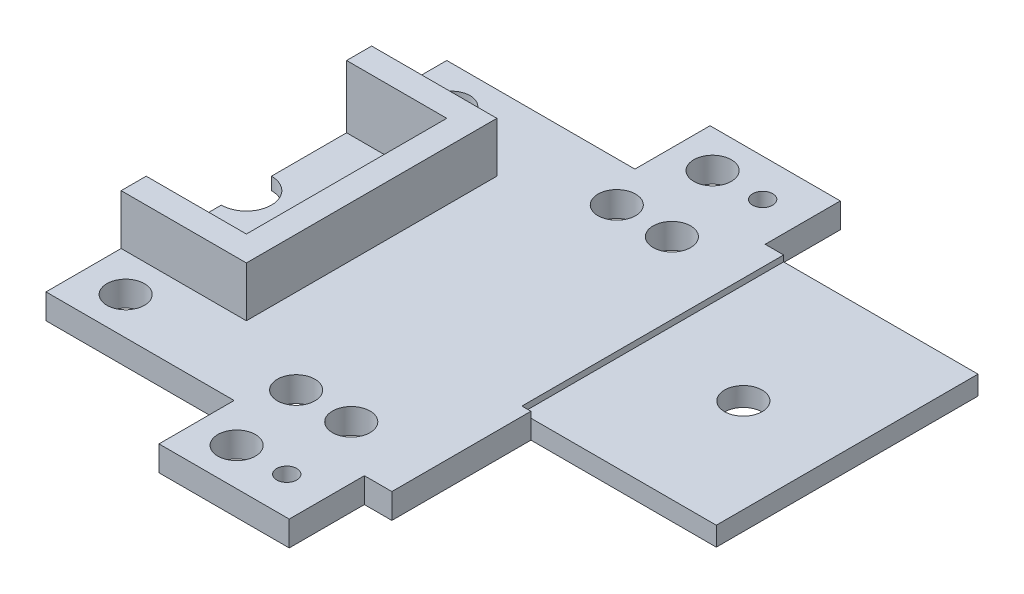
SolidWorks part; units mm, degrees
ref_plane "Front Plane" through (0, 0, 0) normal (0, 0, 1) x (1, 0, 0)
ref_plane "Top Plane" through (0, 0, 0) normal (0, 1, 0) x (1, 0, 0)
ref_plane "Right Plane" through (0, 0, 0) normal (1, 0, 0) x (0, 0, -1)
sketch "Sketch1" plane through (0, 0, 0) normal (0, 1, 0) x (1, 0, 0)
  line L1 (-279.4, -50.8) -> (0, -50.8)
  line L2 (-279.4, -50.8) -> (-279.4, 50.8)
  line L3 (-279.4, 50.8) -> (0, 50.8)
  line L4 (0, -50.8) -> (0, 50.8)
  point P0 (0, 0)
  dimension "D1" = 279.4
  dimension "D2" = 101.6
  dimension "D3" = 50.8
extrude "Boss-Extrude1" add sketch "Sketch1" along normal blind 6.35
sketch "Sketch2" plane through (0, 6.35, 0) normal (0, 1, 0) x (1, 0, 0)
  line L0 (-279.4, 50.8) -> (-279.4, -50.8) construction
  line L2 (0, 50.8) -> (-279.4, 50.8) construction
  circle A0 centre (-258.5106, 0) radius 13.97
  dimension "D1" = 50.8
  dimension "D2" = 27.94
  dimension "D3" = 20.8894
extrude "Boss-Extrude3" add sketch "Sketch2" along normal blind 5.5562
sketch "Sketch9" plane through (0, 11.9062, 0) normal (0, 1, 0) x (1, 0, 0)
  circle A0 centre (-258.5106, 0) radius 11.1125
  dimension "D1" = 22.225
extrude "Cut-Extrude4" cut sketch "Sketch9" against normal blind 4.445
sketch "Sketch10" plane through (0, 0, 0) normal (0, -1, 0) x (-1, 0, 0)
  circle A0 centre (258.5106, 0) radius 11.1125
  dimension "D1" = 22.225
extrude "Cut-Extrude5" cut sketch "Sketch10" against normal blind 5.5562
sketch "Sketch11" plane through (0, 7.4613, 0) normal (0, 1, 0) x (1, 0, 0)
  circle A0 centre (-258.5106, 0) radius 7.9375
  dimension "D1" = 15.875
extrude "Cut-Extrude6" cut sketch "Sketch11" against normal through all
sketch "Sketch12" plane through (0, 6.35, 0) normal (0, 1, 0) x (1, 0, 0)
  line L0 (0, 50.8) -> (-279.4, 50.8) construction
  line L1 (-279.4, 50.8) -> (-279.4, -50.8) construction
  circle A0 centre (-134.6662, 0) radius 6.35
  dimension "D1" = 12.7
  dimension "D2" = 50.8
  dimension "D3" = 144.7338
extrude "Cut-Extrude7" cut sketch "Sketch12" against normal through all
sketch "Sketch22" plane through (0, 6.35, 0) normal (0, 1, 0) x (1, 0, 0)
  line L1 (-102.9162, -31.75) -> (-166.4162, -31.75)
  line L2 (-102.9162, -31.75) -> (-102.9162, 31.75)
  line L3 (-102.9162, 31.75) -> (-166.4162, 31.75)
  line L4 (-166.4162, -31.75) -> (-166.4162, 31.75)
  line L5 (-102.9162, -31.75) -> (-166.4162, 31.75) construction
  line L6 (-102.9162, 31.75) -> (-166.4162, -31.75) construction
  circle A0 centre (-134.6662, 0) radius 6.35 construction
  point P0 (-134.6662, 0)
  dimension "D1" = 63.5
  dimension "D2" = 63.5
extrude "Boss-Extrude7" add sketch "Sketch22" along normal blind 12.7
sketch "Sketch25" plane through (0, 19.05, 0) normal (0, 1, 0) x (1, 0, 0)
  line L1 (-109.2662, -25.4) -> (-160.0662, -25.4)
  line L2 (-109.2662, -25.4) -> (-109.2662, 25.4)
  line L3 (-109.2662, 25.4) -> (-160.0662, 25.4)
  line L4 (-160.0662, -25.4) -> (-160.0662, 25.4)
  line L5 (-109.2662, -25.4) -> (-160.0662, 25.4) construction
  line L6 (-109.2662, 25.4) -> (-160.0662, -25.4) construction
  circle A0 centre (-134.6662, 0) radius 6.35 construction
  point P0 (-134.6662, 0)
  dimension "D1" = 50.8
  dimension "D2" = 50.8
extrude "Cut-Extrude11" cut sketch "Sketch25" against normal blind 15.875
sketch "Sketch32" plane through (0, 6.35, 0) normal (0, 1, 0) x (1, 0, 0)
  line L0 (0, -50.8) -> (0, 50.8) construction
  line L3 (-279.4, -50.8) -> (0, -50.8) construction
  line L5 (0, 50.8) -> (-279.4, 50.8) construction
  circle A0 centre (-67.442, -40.64) radius 4.7625
  circle A1 centre (-81.412, -40.64) radius 4.7625
  circle A2 centre (-67.442, 40.64) radius 4.7625
  circle A3 centre (-81.412, 40.64) radius 4.7625
  dimension "D1" = 10.16
  dimension "D2" = 10.16
  dimension "D3" = 10.16
  dimension "D4" = 10.16
  dimension "D9" = 9.525
  dimension "D10" = 9.525
  dimension "D11" = 9.525
  dimension "D12" = 9.525
  dimension "D5" = 13.97
  dimension "D6" = 13.97
  dimension "D7" = 81.28
  dimension "D8" = 81.412
extrude "Cut-Extrude12" cut sketch "Sketch32" against normal blind 6.35
sketch "Sketch38" plane through (0, 6.35, 0) normal (0, 1, 0) x (1, 0, 0)
  line L0 (0, -50.8) -> (0, 50.8) construction
  line L1 (0, -34.0128) -> (-46.99, -34.0128)
  line L2 (0, -34.0128) -> (0, -15.5426)
  line L3 (0, -15.5426) -> (-46.99, -15.5426)
  line L4 (-46.99, -34.0128) -> (-46.99, -15.5426)
  line L6 (-279.4, -50.8) -> (0, -50.8) construction
  dimension "D1" = 35.2574
  dimension "D2" = 18.4703
  dimension "D3" = 46.99
extrude "Cut-Extrude13" cut sketch "Sketch38" against normal blind 6.35
sketch "Sketch60" plane through (0, 6.35, 0) normal (0, 1, 0) x (1, 0, 0)
  line L1 (-279.4, 50.8) -> (-279.4, -50.8) construction
  line L2 (0, 50.8) -> (-279.4, 50.8) construction
  circle A0 centre (-231.7492, 41.3241) radius 4.7625
  circle A1 centre (-231.7492, -39.3693) radius 4.7625
  circle A2 centre (-173.5092, -39.3693) radius 4.7625
  circle A3 centre (-173.5092, 41.3241) radius 4.7625
  dimension "D1" = 47.6508
  dimension "D5" = 9.525
  dimension "D6" = 9.525
  dimension "D7" = 9.525
  dimension "D8" = 9.525
  dimension "D2" = 58.24
  dimension "D3" = 80.6935
  dimension "D4" = 9.4759
  dimension "D9" = 105.8908
extrude "Cut-Extrude23" cut sketch "Sketch60" against normal up to surface (6.35 mm away) up to face at (-81.5975, 0, 12.3889)
sketch "Sketch64" plane through (0, 6.35, 0) normal (0, 1, 0) x (1, 0, 0)
  line L0 (-279.4, -50.8) -> (0, -50.8) construction
  circle A0 centre (-145.3342, -41.275) radius 4.7625
  circle A1 centre (-123.9982, -41.275) radius 4.7625
  circle A3 centre (-134.6662, 0) radius 6.35 construction
  dimension "D1" = 21.336
  dimension "D3" = 9.525
  dimension "D4" = 9.525
  dimension "D2" = 10.668
  dimension "D5" = 9.525
  dimension "D6" = 9.525
extrude "Cut-Extrude24" cut sketch "Sketch64" against normal through all
mirror "Mirror1" about plane through (0, 0, 0) normal (0, 0, 1) of "Cut-Extrude24"
sketch "Sketch69" plane through (0, 0, 50.8) normal (0, 0, 1) x (1, 0, 0)
  line L0 (-279.4, 6.35) -> (0, 6.35) construction
  line L1 (-86.9754, 6.35) -> (-53.9554, 6.35)
  line L2 (-86.9754, 6.35) -> (-86.9754, 0)
  line L3 (-86.9754, 0) -> (-53.9554, 0)
  line L4 (-53.9554, 6.35) -> (-53.9554, 0)
  line L5 (-279.4, 0) -> (0, 0) construction
  line L7 (0, 6.35) -> (0, 0) construction
  dimension "D1" = 33.02
  dimension "D2" = 53.9554
extrude "Boss-Extrude10" add sketch "Sketch69" along normal blind 19.05
sketch "Sketch70" plane through (0, 6.35, 0) normal (0, 1, 0) x (1, 0, 0)
  line L1 (-86.9754, -69.85) -> (-86.9754, -50.8) construction
  circle A0 centre (-76.8154, -60.325) radius 4.7625
  circle A1 centre (-64.1154, -60.325) radius 2.54
  point P6 (-86.9754, -60.325)
  dimension "D1" = 9.525
  dimension "D3" = 5.08
  dimension "D2" = 10.16
  dimension "D4" = 22.86
extrude "Cut-Extrude26" cut sketch "Sketch70" against normal up to surface (6.35 mm away) up to face at (-145.3342, 0, -46.0375)
mirror "Mirror2" about plane through (0, 0, 0) normal (0, 0, 1) of "Cut-Extrude26", "Boss-Extrude10"
sketch "Sketch76" plane through (0, 6.35, 0) normal (0, 1, 0) x (1, 0, 0)
  line L0 (-279.4, 50.8) -> (-279.4, -50.8) construction
  line L1 (-86.9754, 50.8) -> (-279.4, 50.8) construction
  circle A0 centre (-264.668, 24.13) radius 4.7625
  circle A1 centre (-252.222, 24.13) radius 4.7625
  dimension "D1" = 14.732
  dimension "D2" = 12.446
  dimension "D3" = 9.525
  dimension "D4" = 9.525
  dimension "D5" = 26.67
  dimension "D6" = 26.67
extrude "Cut-Extrude29" cut sketch "Sketch76" against normal up to surface (6.35 mm away) up to face at (-76.8154, 0, -65.0875)
sketch "Sketch77" plane through (0, 6.35, 0) normal (0, 1, 0) x (1, 0, 0)
  line L0 (-53.9554, -50.8) -> (0, -50.8) construction
  line L1 (0, -34.0128) -> (-46.99, -34.0128)
  line L2 (0, -34.0128) -> (0, -50.8)
  line L3 (0, -50.8) -> (-46.99, -50.8)
  line L4 (-46.99, -34.0128) -> (-46.99, -50.8)
  line L5 (-46.99, -15.5426) -> (-46.99, -34.0128) construction
extrude "Cut-Extrude30" cut sketch "Sketch77" against normal up to surface (6.35 mm away) up to face at (-264.668, 0, -28.8925)
sketch "Sketch78" plane through (0, 6.35, 0) normal (0, 1, 0) x (1, 0, 0)
  line L0 (0, -15.5426) -> (-46.99, -15.5426) construction
  line L1 (-49.276, -15.5426) -> (0, -15.5426)
  line L2 (-49.276, -15.5426) -> (-49.276, 50.8)
  line L3 (-49.276, 50.8) -> (0, 50.8)
  line L4 (0, -15.5426) -> (0, 50.8)
  dimension "D1" = 49.276
extrude "Cut-Extrude32" cut sketch "Sketch78" against normal blind 1.524 contours L2 L1 L4 L3
sketch "Sketch79" plane through (0, 4.826, 0) normal (0, 1, 0) x (1, 0, 0)
  line L0 (-46.99, -15.5426) -> (0, -15.5426) construction
  line L1 (0, -15.5426) -> (0, 50.8) construction
  circle A0 centre (-23.876, 15.1914) radius 4.7625
  dimension "D3" = 9.525
  dimension "D1" = 30.734
  dimension "D2" = 23.876
extrude "Cut-Extrude33" cut sketch "Sketch79" against normal up to surface (4.826 mm away) up to face at (-86.8931, 0, 2.2204)
sketch "Sketch80" plane through (0, 3.175, 0) normal (0, 1, 0) x (1, 0, 0)
  line L0 (-134.6662, 0) -> (-134.6662, -50.8)
  line L1 (-134.6662, 0) -> (-134.6662, 50.8)
  line L2 (-86.9754, 50.8) -> (-279.4, 50.8) construction
  line L3 (-279.4, -50.8) -> (-86.9754, -50.8) construction
  point P3 (0, 0)
  point P7 (0, 0)
extrude "Cut-Extrude34" cut sketch "Sketch80" against normal through all and the other way through all
